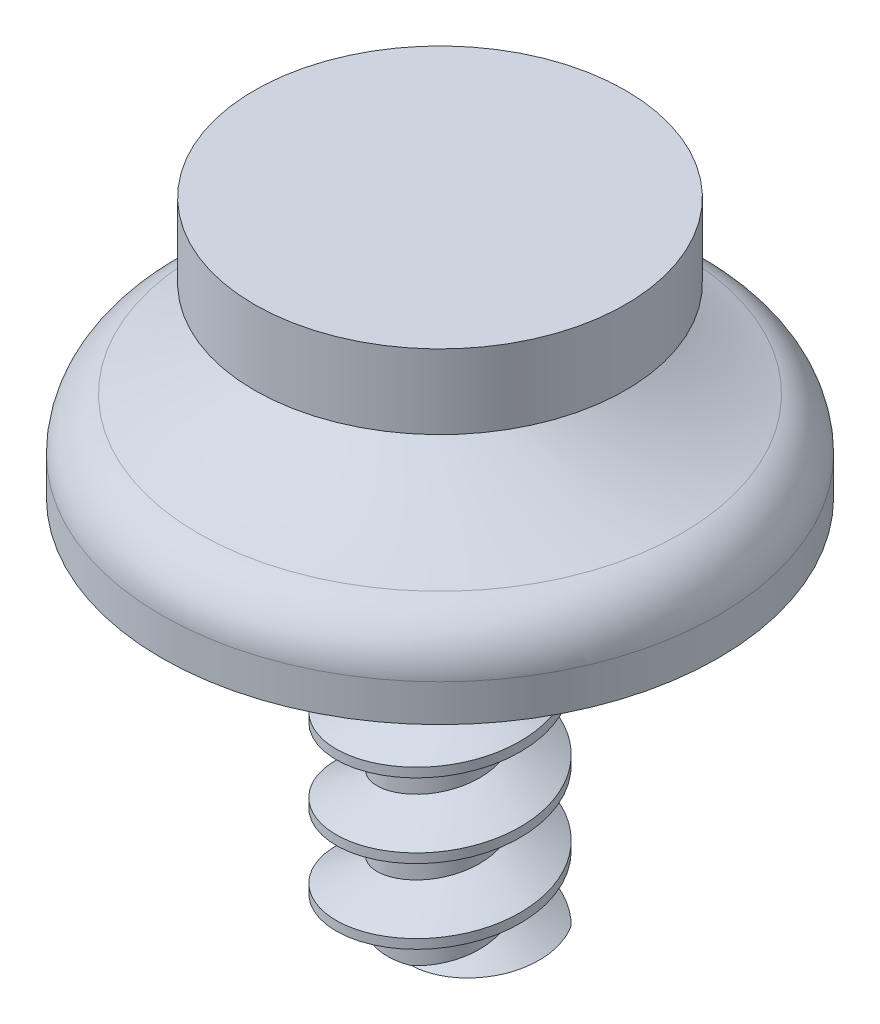
SolidWorks part; units mm, degrees
ref_plane "Front Plane" through (0, 0, 0) normal (0, 0, 1) x (1, 0, 0)
ref_plane "Top Plane" through (0, 0, 0) normal (0, 1, 0) x (1, 0, 0)
ref_plane "Right Plane" through (0, 0, 0) normal (1, 0, 0) x (0, 0, -1)
sketch "Sketch1" plane through (0, 0, 0) normal (0, 1, 0) x (1, 0, 0)
  circle A0 centre (0, 0) radius 5
  dimension "D1" = 10
extrude "Boss-Extrude1" add sketch "Sketch1" along normal blind 20
thread "Thread1" pitch 4 method cut profile "Thread Profile1" start angle 0, offset 5, length 0, pitch 4, diameter 10
ref_plane "Plane1" through (-5, 25, 0) normal (0, 0, 1) x (-1, 0, 0)
sketch "Thread Profile1" plane through (-5, 25, 0) normal (0, 0, 1) x (-1, 0, 0)
  line L0 (0, 0) -> (0, 4) construction
  line L11 (0, 0) -> (0, 3.5)
  line L12 (0, 3.5) -> (-2.1651, 2.25)
  line L13 (-2.1651, 2.25) -> (-2.1651, 1.25)
  line L15 (-2.1651, 1.25) -> (0, 0)
  line L17 (-2.1651, 1.75) -> (0, 1.75) construction
  point P2 (0, 0)
  dimension "Pitch" = 4
  dimension "Profile_Angle" = 60
  dimension "Profile_Land" = 1
  dimension "Profile_Height" = 2.1651
sketch "Sketch14" plane through (0, 20, 0) normal (0, 1, 0) x (1, 0, 0)
  circle A0 centre (0, 0) radius 15
  dimension "D1" = 30
extrude "Boss-Extrude2" add sketch "Sketch14" along normal blind 5
sketch "Sketch15" plane through (0, 25, 0) normal (0, 1, 0) x (1, 0, 0)
  circle A0 centre (0, 0) radius 4.5
  dimension "D1" = 9
extrude "Boss-Extrude3" add sketch "Sketch15" along normal blind 5
sketch "Sketch16" plane through (0, 30, 0) normal (0, 1, 0) x (1, 0, 0)
  circle A0 centre (0, 0) radius 10
  dimension "D1" = 20
extrude "Boss-Extrude4" add sketch "Sketch16" along normal blind 4
fillet "Fillet1" radius 3 1 edges at (0, 25, 15)
fillet "Fillet2" radius 25 1 edges at (0, 25, 4.5)
